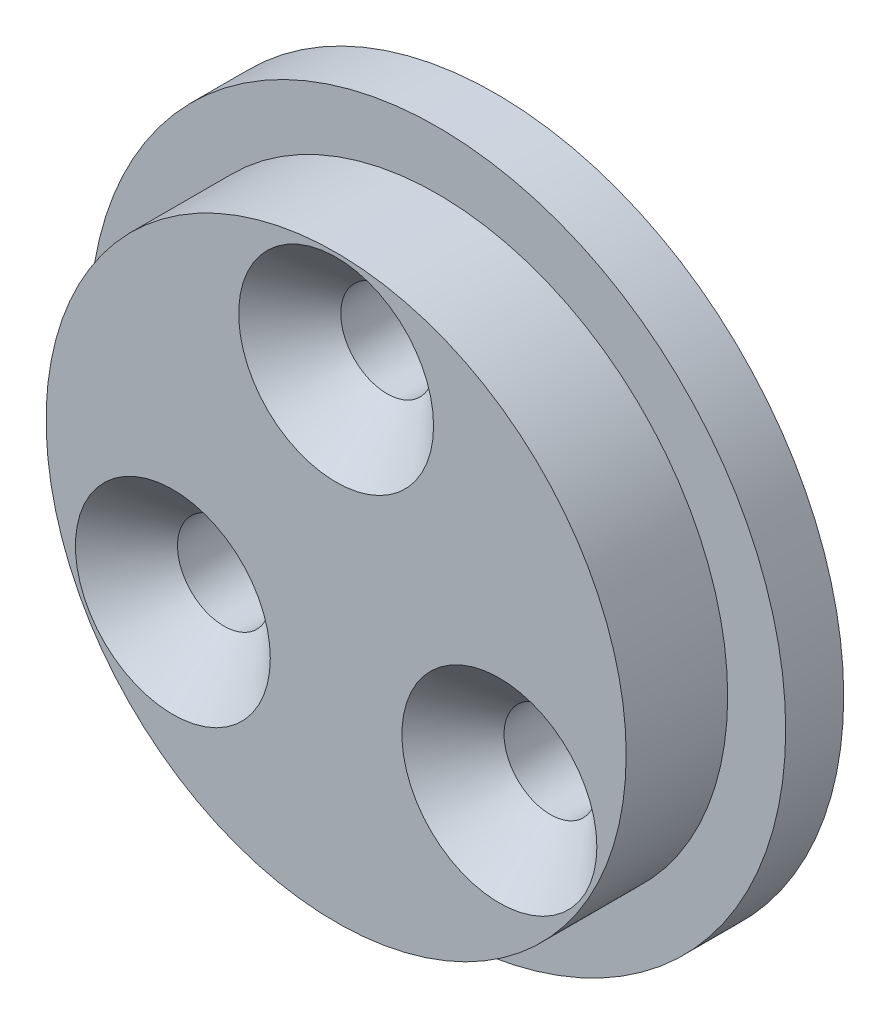
SolidWorks part; units mm, degrees
ref_plane "Front Plane" through (0, 0, 0) normal (0, 0, 1) x (1, 0, 0)
ref_plane "Top Plane" through (0, 0, 0) normal (0, 1, 0) x (1, 0, 0)
ref_plane "Right Plane" through (0, 0, 0) normal (1, 0, 0) x (0, 0, -1)
sketch "Sketch1" plane through (0, 0, 0) normal (0, 1, 0) x (1, 0, 0)
  line L0 (0, 0) -> (0, 23.9376) construction
  line L1 (0, 0) -> (3, 0)
  line L2 (3, 0) -> (3, 3)
  line L4 (10, 3) -> (10, -0.5)
  line L5 (10, -0.5) -> (0, -0.5)
  line L6 (0, -0.5) -> (0, 0)
  line L7 (10, 3) -> (12, 3)
  line L8 (12, 3) -> (12, 5)
  line L9 (9.5, 3) -> (3, 3)
  line L10 (3, 2.5) -> (0, 2.5) construction
  line L11 (9.5, 5) -> (12, 5)
  line L12 (9.5, 5) -> (9.5, 3)
  point P14 (12, 3.9565)
  point P16 (12, 3.4661)
  point P17 (12, 5.2641)
  point P18 (12.1825, 5.2641)
  dimension "D1" = 20
  dimension "D2" = 6
  dimension "D3" = 3
  dimension "D4" = 2.5
  dimension "D5" = 0.5
  dimension "D6" = 24
  dimension "D7" = 19
  dimension "D8" = 2
revolve "Revolve1" add sketch "Sketch1" angle 360 about L0
sketch "Sketch2" plane through (0, 0, 0.5) normal (0, 0, 1) x (1, 0, 0)
sketch "Sketch4" plane through (0, 0, 0.5) normal (0, 0, 1) x (1, 0, 0)
sketch "Sketch6" plane through (0, 0, 0.5) normal (0, 0, 1) x (1, 0, 0)
  circle A0 centre (0, 0) radius 6.5 construction
  point P0 (0, 6.5)
  point P20 (5.6292, -3.25)
  point P21 (-5.6292, -3.25)
  point P23 (-5.2207, -3.8722)
  point P24 (5.6414, -3.2287)
  dimension "D1" = 13
  dimension "D2" = 3
hole_wizard "CSK for M3 SFHCS1" positions "Sketch6" profile "Sketch5" countersink size "M3" standard "ANSI Metric" end condition through all
sketch "Sketch5" plane through (0, 6.5, 0.5) normal (1, 0, 0) x (0, -1, 0)
  line L0 (0, 0) -> (0, 5.5)
  line L1 (0, 5.5) -> (1.6, 5.5)
  line L2 (1.6, 5.5) -> (1.6, 1.76)
  line L3 (1.6, 1.76) -> (3.36, 0)
  line L5 (3.36, 0) -> (0, 0)
  line L6 (-1.6, 1.76) -> (-3.36, 0) construction
  line L11 (0, -6.35) -> (0, 107.95) construction
  dimension "Thru Hole Dia." = 3.2
  dimension "Thru Hole Depth" = 5.5
  dimension "Near C'Sink Dia." = 6.72
  dimension "Near C'Sink Angle" = 90
chamfer "Chamfer1" distance 0.8 angle 45 1 edges at (9.5, 0, -5)
